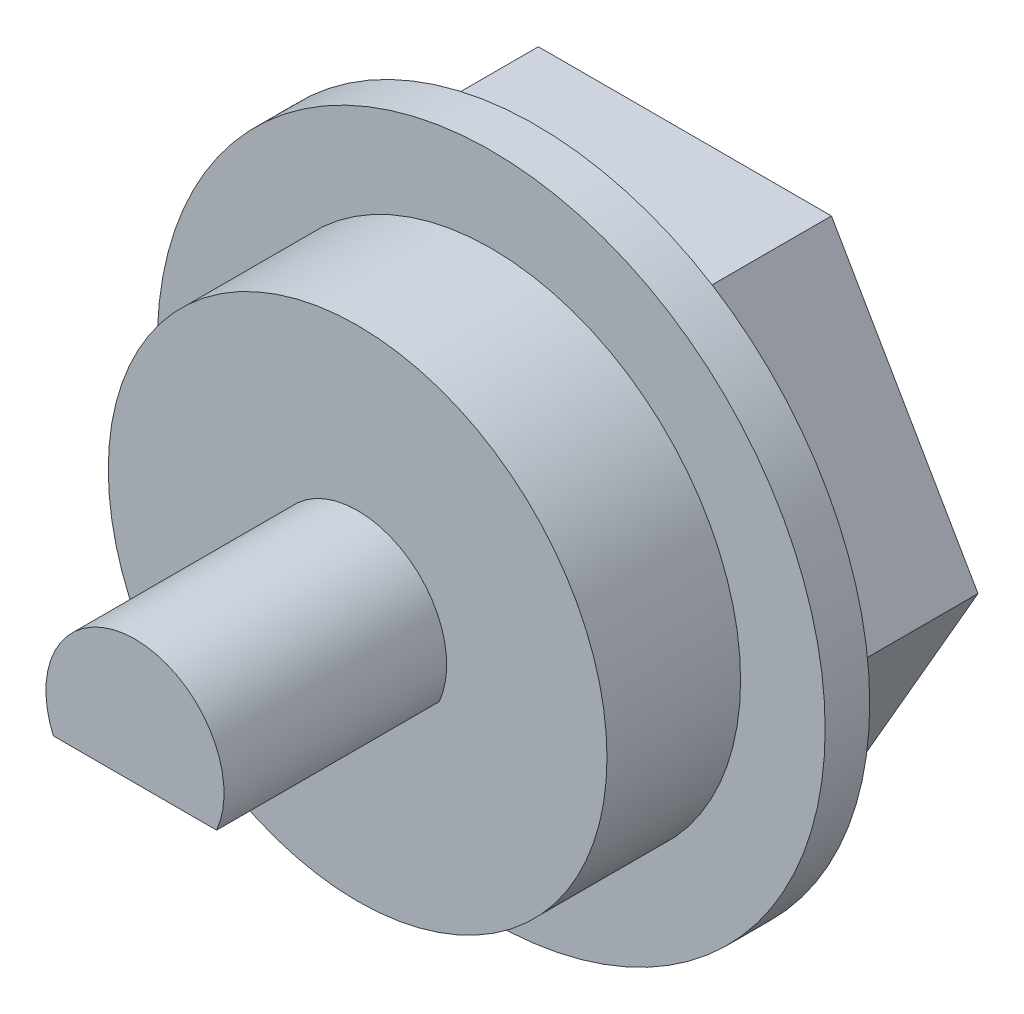
SolidWorks part; units mm, degrees
note: The reader was unsure of these and kept them because the rebuilt part matched: shared geometry of "Sketch1<3>", "Sketch1<4>".
ref_plane "Front Plane" through (0, 0, 0) normal (0, 0, 1) x (1, 0, 0)
ref_plane "Top Plane" through (0, 0, 0) normal (0, 1, 0) x (1, 0, 0)
ref_plane "Right Plane" through (0, 0, 0) normal (1, 0, 0) x (0, 0, -1)
sketch "Sketch1" plane through (0, 0, 0) normal (0, 0, 1) x (1, 0, 0)
  line L0 (-3.2909, -5.7) -> (3.2909, -5.7)
  line L1 (3.2909, -5.7) -> (6.5818, 0)
  line L2 (6.5818, 0) -> (3.2909, 5.7)
  line L3 (3.2909, 5.7) -> (-3.2909, 5.7)
  line L4 (-3.2909, 5.7) -> (-6.5818, 0)
  line L5 (-6.5818, 0) -> (-3.2909, -5.7)
  circle A0 centre (0, 0) radius 5.6
  circle A1 centre (0, 0) radius 7.5
  point P8 (0, 0)
  point P10 (0, 5.7)
  dimension "D3" = 15
  dimension "D4" = 11.2
  dimension "D1" = 120
  dimension "D2" = 11.4
extrude "Boss-Extrude1" add sketch "Sketch1" along normal blind 1 contours L4 L5 L0 L1 L2 L3 A1 | A0 | A1 A0
extrude "Boss-Extrude2" add sketch "Sketch1<3>" against normal blind 3.35 contours A1 A0 | A0
sketch "Sketch1<3>" plane through (0, 0, 0) normal (0, 0, 1) x (1, 0, 0) same geometry as "Sketch1"
ref_plane "Plane1" through (0, 0, 0.5) normal (0, 0, 1) x (1, 0, 0)
extrude "Boss-Extrude3" add sketch "Sketch1<4>" along normal blind 3 from surface at 1 contours A0 starting at face at (7.5, 0, 1)
sketch "Sketch1<4>" plane through (0, 0, 0) normal (0, 0, 1) x (1, 0, 0) same geometry as "Sketch1"
sketch "Sketch2" plane through (0, 0, 4) normal (0, 0, 1) x (1, 0, 0)
  line L0 (-1.833, -0.8) -> (1.833, -0.8)
  arc A0 (-1.833, -0.8) -> (1.833, -0.8) centre (0, 0) cw
  dimension "D1" = 2
  dimension "D2" = 0.8
extrude "Boss-Extrude4" add sketch "Sketch2" along normal mid plane 10
